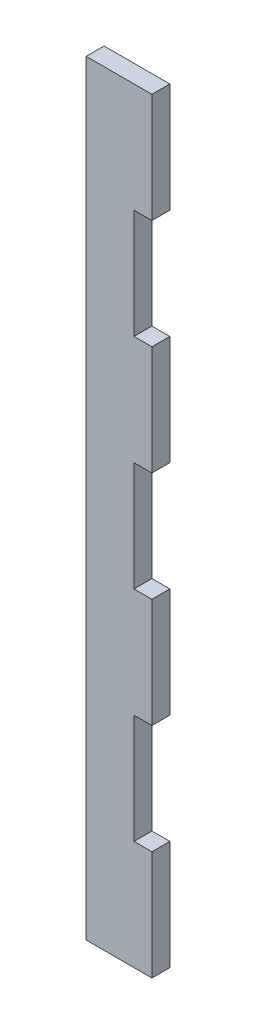
SolidWorks part; units mm, degrees
ref_plane "Front Plane" through (0, 0, 0) normal (0, 0, 1) x (1, 0, 0)
ref_plane "Top Plane" through (0, 0, 0) normal (0, 1, 0) x (1, 0, 0)
ref_plane "Right Plane" through (0, 0, 0) normal (1, 0, 0) x (0, 0, -1)
sketch "Sketch1" plane through (0, 0, 0) normal (0, 0, 1) x (1, 0, 0)
  line L0 (0, 101.6) -> (0, -101.6) construction
  line L1 (-6.35, 101.6) -> (6.35, 101.6)
  line L2 (-6.35, 101.6) -> (-6.35, -101.6)
  line L3 (-6.35, -101.6) -> (6.35, -101.6)
  line L4 (6.35, 101.6) -> (6.35, -101.6)
  line L5 (6.35, 72.5714) -> (6.35, 43.5429)
  line L6 (6.35, 101.6) -> (11.1125, 101.6)
  line L7 (6.35, 101.6) -> (6.35, 72.5714)
  line L8 (6.35, 72.5714) -> (11.1125, 72.5714)
  line L9 (11.1125, 101.6) -> (11.1125, 72.5714)
  line L10 (6.35, 72.5714) -> (11.1125, 72.5714)
  line L11 (11.1125, 72.5714) -> (11.1125, 43.5429)
  line L12 (6.35, 43.5429) -> (11.1125, 43.5429)
  line L13 (6.35, 43.5429) -> (6.35, 14.5143)
  line L14 (6.35, 43.5429) -> (11.1125, 43.5429)
  line L15 (11.1125, 43.5429) -> (11.1125, 14.5143)
  line L16 (6.35, 14.5143) -> (11.1125, 14.5143)
  line L17 (6.35, 14.5143) -> (6.35, -14.5143)
  line L18 (6.35, 14.5143) -> (11.1125, 14.5143)
  line L19 (11.1125, 14.5143) -> (11.1125, -14.5143)
  line L20 (6.35, -14.5143) -> (11.1125, -14.5143)
  line L21 (6.35, -14.5143) -> (6.35, -43.5429)
  line L22 (6.35, -14.5143) -> (11.1125, -14.5143)
  line L23 (11.1125, -14.5143) -> (11.1125, -43.5429)
  line L24 (6.35, -43.5429) -> (11.1125, -43.5429)
  line L25 (6.35, -43.5429) -> (6.35, -72.5714)
  line L26 (6.35, -43.5429) -> (11.1125, -43.5429)
  line L27 (11.1125, -43.5429) -> (11.1125, -72.5714)
  line L28 (6.35, -72.5714) -> (11.1125, -72.5714)
  line L29 (6.35, -72.5714) -> (6.35, -101.6)
  line L30 (6.35, -72.5714) -> (11.1125, -72.5714)
  line L31 (11.1125, -72.5714) -> (11.1125, -101.6)
  line L32 (6.35, -101.6) -> (11.1125, -101.6)
  point P6 (0, 0)
  dimension "D2" = 12.7
  dimension "D1" = 203.2
  dimension "D3" = 29.0286
  dimension "D4" = 4.7625
  dimension "D5" = 7
extrude "Boss-Extrude1" add sketch "Sketch1" along normal blind 4.7625 contours L0 L1 L2 L3 | L1 L0 L3 L4 | L9 L6 L4 L8 | L4 L16 L15 L12 | L4 L24 L23 L20 | L4 L32 L31 L28 region at (3.175, 0, 0) region at (-3.175, 0, 0) region at (8.7312, 87.0857, 0) region at (8.7313, -87.0857, 0) region at (8.7313, 29.0286, 0) region at (8.7313, -29.0286, 0)
equation "\"Height\"= 12in"
equation "\"Depth\"= 7in"
equation "\"WallThickness\"= 0.1875in"
equation "\"FloorThickness\"= 0.1875in"
equation "\"Width\"= 30in"
equation "\"D1@Boss-Extrude1\"=\"WallThickness\""
equation "\"D3@Sketch1\"=\"D1@Sketch1\"/\"D5@Sketch1\""
equation "\"D4@Sketch1\"=\"WallThickness\""
